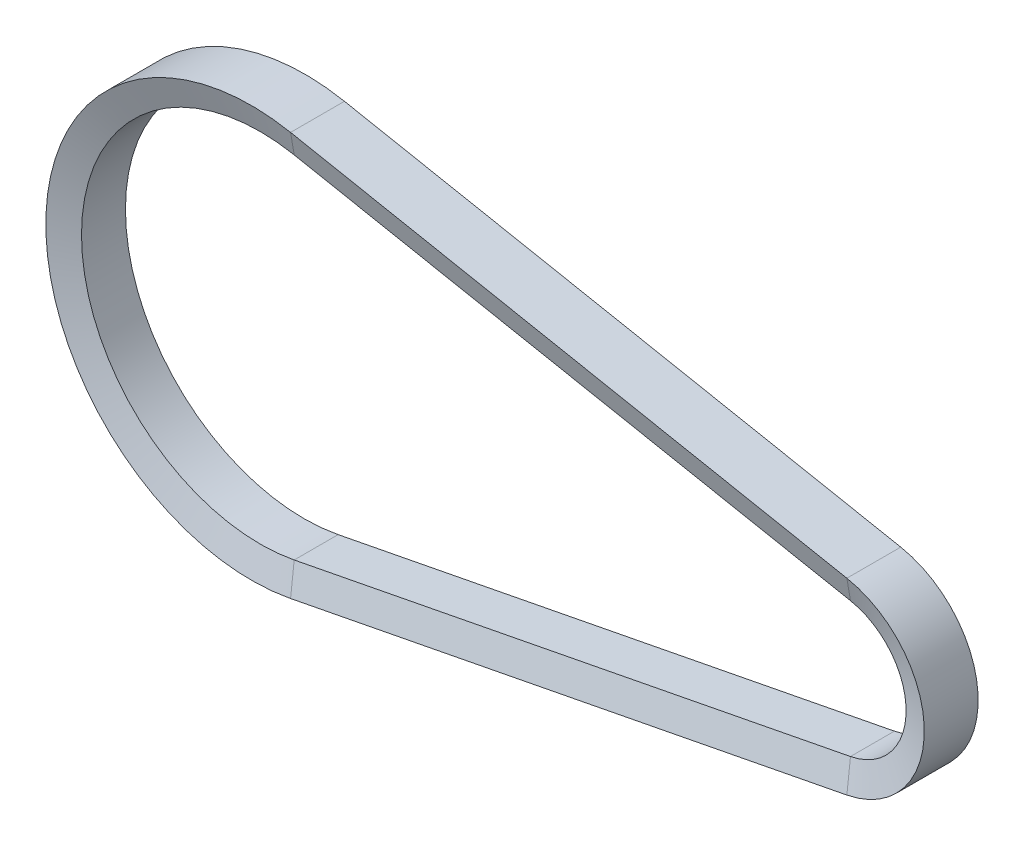
SolidWorks part; units mm, degrees
ref_plane "Front Plane" through (0, 0, 0) normal (0, 0, 1) x (1, 0, 0)
ref_plane "Top Plane" through (0, 0, 0) normal (0, 1, 0) x (1, 0, 0)
ref_plane "Right Plane" through (0, 0, 0) normal (1, 0, 0) x (0, 0, -1)
sketch "Sketch4" plane through (0, 0, 0) normal (0, 0, 1) x (1, 0, 0)
  line L0 (12.381, 63.81) -> (214.7619, 24.5423)
  line L1 (14.2476, -73.4305) -> (216.6286, -34.1629)
  line L2 (12.381, -63.81) -> (214.7619, -24.5423)
  line L3 (14.2476, 73.4305) -> (216.6286, 34.1629)
  arc A0 (12.381, 63.81) -> (12.381, -63.81) centre (0, 0) ccw
  arc A1 (214.7619, -24.5423) -> (214.7619, 24.5423) centre (210, 0) ccw
  arc A2 (14.2476, 73.4305) -> (14.2476, -73.4305) centre (0, 0) ccw
  arc A3 (216.6286, -34.1629) -> (216.6286, 34.1629) centre (210, 0) ccw
  dimension "D2" = 65
  dimension "D3" = 25
  dimension "D1" = 210
  dimension "D4" = 9.8
extrude "Boss-Extrude2" add sketch "Sketch4" along normal blind 19.6
chamfer "Chamfer1" distance 9.8 angle 18 4 edges at (235, 0, 19.6) (113.5714, -44.1761, 19.6) (-65, 0, 19.6) (113.5714, 44.1761, 19.6) first distance on face at (100.219, 0, 19.6)
chamfer "Chamfer2" distance 9.8 angle 2.5 4 edges at (235, 0, 0) (113.5714, -44.1761, 0) (-65, 0, 0) (113.5714, 44.1761, 0) first distance on face at (100.219, 0, 0)
